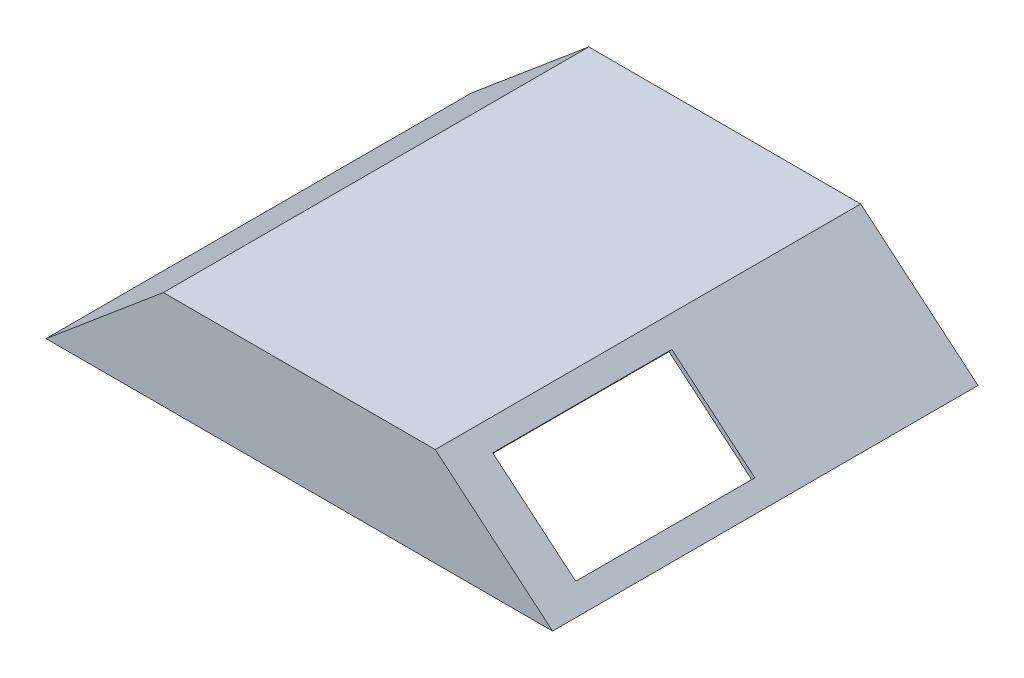
SolidWorks part; units mm, degrees
ref_plane "Alzado" through (0, 0, 0) normal (0, 0, 1) x (1, 0, 0)
ref_plane "Planta" through (0, 0, 0) normal (0, 1, 0) x (1, 0, 0)
ref_plane "Vista lateral" through (0, 0, 0) normal (1, 0, 0) x (0, 0, -1)
sketch "Croquis1" plane through (0, 0, 0) normal (0, 0, 1) x (1, 0, 0)
  line L0 (-55, 0) -> (-56.5547, 0)
  line L1 (-56.5547, 0) -> (-30.3643, 22)
  line L2 (-30, 21) -> (30, 21)
  line L3 (-30, 21) -> (-55, 0)
  line L4 (30.3643, 22) -> (-30.3643, 22)
  line L5 (0, 0) -> (0, 33.9502) construction
  line L6 (30, 21) -> (55, 0)
  line L7 (56.5547, 0) -> (30.3643, 22)
  line L8 (55, 0) -> (56.5547, 0)
  point P10 (0, 22)
  point P12 (0, 21)
  dimension "D1" = 1
  dimension "D2" = 30
  dimension "D3" = 55
  dimension "D4" = 1
  dimension "D5" = 21
extrude "Saliente-Extruir1" add sketch "Croquis1" along normal blind 94
sketch "Croquis3" plane through (23.3965, 27.8529, 0) normal (0.6432, 0.7657, 0) x (0, 0, -1)
  line L0 (-94, -9.0998) -> (0, -9.0998) construction
  line L1 (-86, -14.0998) -> (-46, -14.0998)
  line L2 (-86, -14.0998) -> (-86, -38.3042)
  line L3 (-86, -38.3042) -> (-46, -38.3042)
  line L4 (-46, -14.0998) -> (-46, -38.3042)
  line L5 (-94, -43.3042) -> (0, -43.3042) construction
  line L6 (-94, -43.3042) -> (-94, -9.0998) construction
  point P8 (-94, -26.202)
  dimension "D1" = 5
  dimension "D2" = 40
  dimension "D3" = 5
  dimension "D4" = 8
extrude "Cortar-Extruir2" cut sketch "Croquis3" against normal up to next
sketch "Croquis4" plane through (0, 0, 94) normal (0, 0, 1) x (1, 0, 0)
  line L0 (-56.5547, 0) -> (56.5547, 0)
  line L1 (56.5547, 0) -> (30.3643, 22)
  line L2 (30.3643, 22) -> (-30.3643, 22)
  line L3 (-30.3643, 22) -> (-56.5547, 0)
extrude "Saliente-Extruir2" add sketch "Croquis4" along normal blind 1
